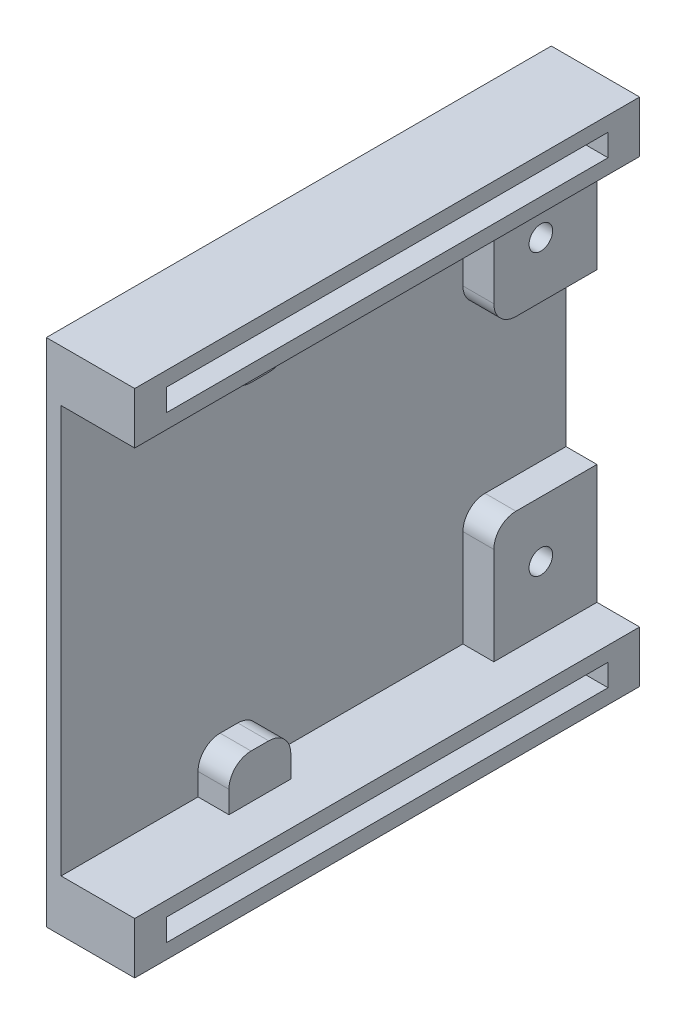
SolidWorks part; units mm, degrees
ref_plane "Front Plane" through (0, 0, 0) normal (1, 0, 0) x (0, 1, 0)
ref_plane "Top Plane" through (0, 0, 0) normal (0, 0, 1) x (0, 1, 0)
ref_plane "Right Plane" through (0, 0, 0) normal (0, 1, 0) x (-1, 0, 0)
sketch "Sketch1" plane through (0, 0, 0) normal (1, 0, 0) x (0, 1, 0)
  line L5 (-17.335, 17.145) -> (17.335, 17.145)
  line L7 (-17.335, 17.145) -> (-17.335, -17.145)
  line L8 (-17.335, -17.145) -> (17.335, -17.145)
  line L9 (17.335, 17.145) -> (17.335, -17.145)
  line L10 (-17.335, 17.145) -> (17.335, -17.145) construction
  line L11 (-17.335, -17.145) -> (17.335, 17.145) construction
  line L12 (-13.335, 17.145) -> (13.335, 17.145) construction
  line L13 (-13.335, 17.145) -> (-13.335, -17.145) construction
  line L14 (-13.335, -17.145) -> (13.335, -17.145) construction
  line L15 (13.335, 17.145) -> (13.335, -17.145) construction
  line L16 (-13.335, 17.145) -> (13.335, -17.145) construction
  line L17 (-13.335, -17.145) -> (13.335, 17.145) construction
  point P0 (0, 0)
  point P6 (0, 0)
  dimension "D1" = 34.67
  dimension "D2" = 34.29
  dimension "D3" = 34.29
  dimension "D4" = 26.67
extrude "Boss-Extrude1" add sketch "Sketch1" along normal blind 1
sketch "Sketch3" plane through (1, 0, 0) normal (1, 0, 0) x (0, 1, 0)
  line L0 (-17.335, -17.145) -> (17.335, -17.145) construction
  line L1 (-17.335, 17.145) -> (-13.835, 17.145)
  line L2 (-17.335, 17.145) -> (-17.335, -17.145)
  line L3 (-17.335, -17.145) -> (-13.835, -17.145)
  line L4 (-13.835, 17.145) -> (-13.835, -17.145)
  line L5 (17.335, 17.145) -> (-17.335, 17.145) construction
  line L6 (17.335, -17.145) -> (13.835, -17.145)
  line L7 (17.335, -17.145) -> (17.335, 17.145)
  line L8 (17.335, 17.145) -> (13.835, 17.145)
  line L9 (13.835, -17.145) -> (13.835, 17.145)
  line M3 (17.335, -17.145) -> (17.335, 17.145)
  line M4 (17.335, 17.145) -> (-17.335, 17.145)
  line M5 (-17.335, 17.145) -> (-17.335, -17.145)
  line M6 (-17.335, -17.145) -> (17.335, -17.145)
  dimension "D1" = 3.5
extrude "Boss-Extrude2" add sketch "Sketch3" along normal blind 5 contours L4 M4 M5 M6 | L9 M6 M3 M4 region at (1, -15.585, 0) region at (1, 15.585, 0)
sketch "Sketch5" plane through (6, 0, 0) normal (1, 0, 0) x (0, 1, 0)
  line L0 (0, 0) -> (0, 50000) construction
  line L1 (-16.335, -15) -> (-14.835, -15)
  line L2 (-16.335, -15) -> (-16.335, 15)
  line L3 (-16.335, 15) -> (-14.835, 15)
  line L4 (-14.835, -15) -> (-14.835, 15)
  line L5 (-16.335, -15) -> (-14.835, 15) construction
  line L6 (-16.335, 15) -> (-14.835, -15) construction
  line L7 (-17.335, 0) -> (-15.585, 0) construction
  line L8 (-17.335, 17.145) -> (-17.335, -17.145) construction
  line L9 (-15.585, 0) -> (-13.835, 0) construction
  line L10 (-13.835, 17.145) -> (-13.835, -17.145) construction
  line L11 (15.585, 0) -> (13.835, 0) construction
  line L12 (17.335, 0) -> (15.585, 0) construction
  line L13 (16.335, 15) -> (14.835, -15) construction
  line L14 (16.335, -15) -> (14.835, 15) construction
  line L15 (14.835, -15) -> (14.835, 15)
  line L16 (16.335, 15) -> (14.835, 15)
  line L17 (16.335, -15) -> (16.335, 15)
  line L18 (16.335, -15) -> (14.835, -15)
  point P0 (-15.585, 0)
  point P22 (15.585, 0)
  dimension "D1" = 1.5
  dimension "D2" = 30
extrude "Cut-Extrude1" cut sketch "Sketch5" against normal through all both and the other way through all
sketch "Sketch6" plane through (1, 0, 0) normal (1, 0, 0) x (0, 1, 0)
  line L0 (-13.835, 17.145) -> (-13.835, -17.145) construction
  line L1 (-13.835, 7.845) -> (-10.835, 7.845)
  line L2 (-13.835, 7.845) -> (-13.835, 3.645)
  line L3 (-13.835, 3.645) -> (-10.835, 3.645)
  line L4 (-10.835, 7.845) -> (-10.835, 3.645)
  line L5 (0, 0) -> (0, -49383.4727) construction
  line L6 (-13.835, -17.145) -> (-5.725, -17.145)
  line L7 (-13.835, -17.145) -> (-13.835, -10.145)
  line L8 (-13.835, -10.145) -> (-5.725, -10.145)
  line L9 (-5.725, -17.145) -> (-5.725, -10.145)
  line L10 (13.835, 17.145) -> (-13.835, 17.145) construction
  line L11 (5.725, -17.145) -> (5.725, -10.145)
  line L12 (13.835, -10.145) -> (5.725, -10.145)
  line L13 (13.835, -17.145) -> (13.835, -10.145)
  line L14 (13.835, -17.145) -> (5.725, -17.145)
  line L15 (10.835, 7.845) -> (10.835, 3.645)
  line L16 (13.835, 3.645) -> (10.835, 3.645)
  line L17 (13.835, 7.845) -> (13.835, 3.645)
  line L18 (13.835, 7.845) -> (10.835, 7.845)
  dimension "D1" = 5.725
  dimension "D2" = 7
  dimension "D3" = 9.3
  dimension "D4" = 13.5
  dimension "D5" = 3
extrude "Boss-Extrude3" add sketch "Sketch6" along normal blind 2.1
fillet "Fillet1" radius 1.5 6 edges at (2.05, 10.835, 3.645) (2.05, 10.835, 7.845) (2.05, -10.835, 3.645) (2.05, -10.835, 7.845) (2.05, 5.725, -10.145) (2.05, -5.725, -10.145)
sketch "Sketch7" plane through (3.1, 0, 0) normal (1, 0, 0) x (0, 1, 0)
  line L0 (0, 0) -> (0, -50000) construction
  line L2 (-13.835, -17.145) -> (-5.725, -17.145) construction
  circle A0 centre (-9.525, -13.335) radius 0.8
  circle A1 centre (9.525, -13.335) radius 0.8
  dimension "D3" = 1.6
  dimension "D1" = 3.81
  dimension "D2" = 9.525
extrude "Cut-Extrude2" cut sketch "Sketch7" against normal through all both and the other way through all contours A0 | A1 region at (3.1, -9.525, -13.335) region at (3.1, 9.525, -13.335)
equation "\"PCB_Width\"= 1.05in"
equation "\"PCB_Length\"= 1.35in"
equation "\"PCB_Thickness\"= 1.50404mm"
equation "\"USB_Height\"= 3.36mm"
equation "\"ZIF_Height\"= 2mm"
equation "\"Case_Thickness\"= 5mm"
